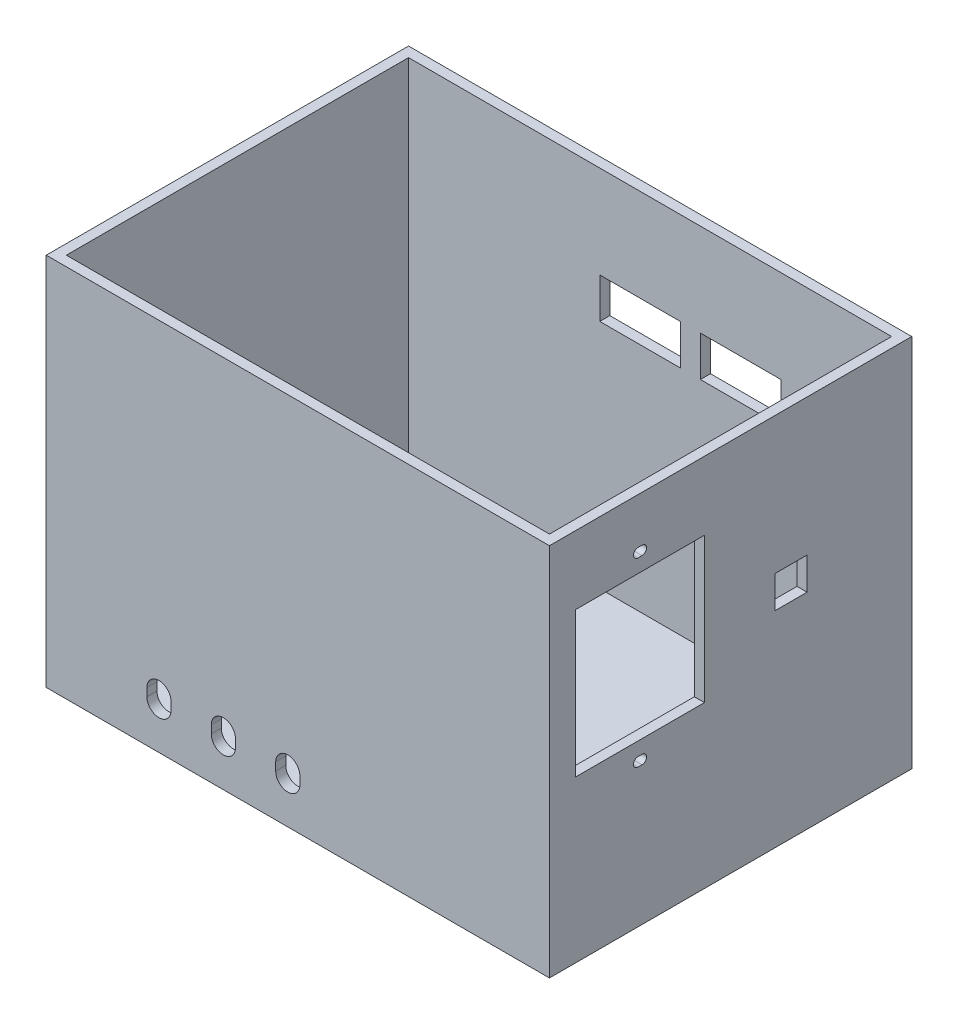
SolidWorks part; units mm, degrees
ref_plane "Front Plane" through (0, 0, 0) normal (0, 0, 1) x (1, 0, 0)
ref_plane "Top Plane" through (0, 0, 0) normal (0, 1, 0) x (1, 0, 0)
ref_plane "Right Plane" through (0, 0, 0) normal (1, 0, 0) x (0, 0, -1)
sketch "Sketch1" plane through (0, 0, 0) normal (0, 1, 0) x (1, 0, 0)
  line L0 (60, 42.5) -> (-60, 42.5)
  line L1 (62.5, 45) -> (-62.5, 45)
  line L2 (62.5, 45) -> (62.5, -45)
  line L3 (62.5, -45) -> (-62.5, -45)
  line L4 (-62.5, 45) -> (-62.5, -45)
  line L5 (62.5, 45) -> (-62.5, -45) construction
  line L6 (62.5, -45) -> (-62.5, 45) construction
  line L7 (-60, 42.5) -> (-60, -42.5)
  line L8 (60, -42.5) -> (-60, -42.5)
  line L9 (60, 42.5) -> (60, -42.5)
  point P0 (0, 0)
  dimension "D1" = 90
  dimension "D2" = 125
  dimension "D3" = 2.5
extrude "Boss-Extrude1" add sketch "Sketch1" along normal blind 2.5 contours L9 L0 L7 L8 | L1 L4 L3 L2 L0 L9 L8 L7 region at (0, 0, 0) region at (60.9597, 0, 0)
extrude "Boss-Extrude2" add sketch "Sketch1<3>" along normal blind 93
sketch "Sketch1<3>" plane through (0, 0, 0) normal (0, 1, 0) x (1, 0, 0) same geometry as "Sketch1"
sketch "Sketch2" plane through (62.5, 0, 0) normal (1, 0, 0) x (0, 0, -1)
  line L0 (0, 93) -> (0, 0) construction
  line L1 (-45, 93) -> (45, 93) construction
  line L2 (-23, 80.5) -> (-22, 80.5) construction
  line L3 (-6.5, 40) -> (-38.5, 40)
  line L4 (-6.5, 40) -> (-6.5, 76)
  line L5 (-6.5, 76) -> (-38.5, 76)
  line L6 (-38.5, 40) -> (-38.5, 76)
  line L7 (-6.5, 40) -> (-38.5, 76) construction
  line L8 (-6.5, 76) -> (-38.5, 40) construction
  line L11 (-23, 81.625) -> (-22, 81.625)
  line L12 (-23, 79.375) -> (-22, 79.375)
  line L13 (-48.2126, 58) -> (-0.6327, 58) construction
  line L14 (-23, 35.5) -> (-22, 35.5) construction
  line L15 (-23, 34.375) -> (-22, 34.375)
  line L16 (-23, 36.625) -> (-22, 36.625)
  arc A2 (-23, 81.625) -> (-23, 79.375) centre (-23, 80.5) ccw
  arc A3 (-22, 79.375) -> (-22, 81.625) centre (-22, 80.5) ccw
  arc A4 (-23, 34.375) -> (-23, 36.625) centre (-23, 35.5) cw
  arc A5 (-22, 36.625) -> (-22, 34.375) centre (-22, 35.5) cw
  point P5 (-22.5, 58)
  point P12 (-22.5, 80.5)
  point P17 (-22.5, 81.625)
  point P22 (-22.5, 35.5)
  point P35 (22.5, 35.5)
  point P42 (22.5, 80.5)
  point P47 (22.5, 58)
  dimension "D1" = 32
  dimension "D2" = 36
  dimension "D3" = 22.5
  dimension "D4" = 35
  dimension "D5" = 16
  dimension "D6" = 2.25
  dimension "D7" = 45
  dimension "D8" = 1
extrude "Cut-Extrude1" cut sketch "Sketch2" against normal blind 5
sketch "Sketch5" plane through (0, 0, 45) normal (0, 0, 1) x (1, 0, 0)
  line L0 (-62.5, 93) -> (-62.5, 0) construction
  line L1 (62.5, 0) -> (-62.5, 0) construction
  line L2 (-34.5, 10.5) -> (-34.5, 12.5) construction
  line L3 (-37.5, 10.5) -> (-37.5, 12.5)
  line L4 (-31.5, 10.5) -> (-31.5, 12.5)
  line L5 (-18.5, 10.5) -> (-18.5, 12.5) construction
  line L6 (-21.5, 10.5) -> (-21.5, 12.5)
  line L7 (-15.5, 10.5) -> (-15.5, 12.5)
  line L8 (-2.5, 10.5) -> (-2.5, 12.5) construction
  line L9 (-5.5, 10.5) -> (-5.5, 12.5)
  line L10 (0.5, 10.5) -> (0.5, 12.5)
  circle A0 centre (-34.5, 11.5) radius 3 construction
  arc A3 (-37.5, 10.5) -> (-31.5, 10.5) centre (-34.5, 10.5) ccw
  arc A4 (-31.5, 12.5) -> (-37.5, 12.5) centre (-34.5, 12.5) ccw
  arc A5 (-21.5, 10.5) -> (-15.5, 10.5) centre (-18.5, 10.5) ccw
  arc A6 (-15.5, 12.5) -> (-21.5, 12.5) centre (-18.5, 12.5) ccw
  arc A7 (-5.5, 10.5) -> (0.5, 10.5) centre (-2.5, 10.5) ccw
  arc A8 (0.5, 12.5) -> (-5.5, 12.5) centre (-2.5, 12.5) ccw
  point P8 (-34.5, 11.5)
  point P16 (-18.5, 11.5)
  point P23 (-2.5, 11.5)
  dimension "D1" = 6
  dimension "D2" = 28
  dimension "D3" = 11.5
  dimension "D4" = 6
  dimension "D5" = 2
  dimension "D6" = 3
extrude "Cut-Extrude2" cut sketch "Sketch5" against normal blind 10
sketch "Sketch6" plane through (62.5, 0, 0) normal (1, 0, 0) x (0, 0, -1)
  line L0 (45, 93) -> (45, 0) construction
  line L1 (11, 59) -> (19, 59)
  line L2 (11, 59) -> (11, 51)
  line L3 (11, 51) -> (19, 51)
  line L4 (19, 59) -> (19, 51)
  line L5 (11, 59) -> (19, 51) construction
  line L6 (11, 51) -> (19, 59) construction
  line L7 (-45, 93) -> (45, 93) construction
  line L8 (30, 35) -> (0, 35) construction
  line L9 (30, 35) -> (30, 75) construction
  line L10 (30, 75) -> (0, 75) construction
  line L11 (0, 35) -> (0, 75) construction
  line L12 (30, 35) -> (0, 75) construction
  line L13 (30, 75) -> (0, 35) construction
  point P0 (15, 55)
  point P7 (15, 55)
  dimension "D1" = 30
  dimension "D2" = 8
  dimension "D3" = 8
  dimension "D4" = 30
  dimension "D5" = 40
  dimension "D6" = 38
extrude "Cut-Extrude3" cut sketch "Sketch6" against normal blind 10
sketch "Sketch7" plane through (0, 0, -45) normal (0, 0, -1) x (-1, 0, 0)
  line L0 (-62.5, 0) -> (62.5, 0) construction
  line L1 (-32.5, 70) -> (-12.5, 70)
  line L2 (-32.5, 70) -> (-32.5, 60)
  line L3 (-32.5, 60) -> (-12.5, 60)
  line L4 (-12.5, 70) -> (-12.5, 60)
  line L5 (-32.5, 70) -> (-12.5, 60) construction
  line L6 (-32.5, 60) -> (-12.5, 70) construction
  line L7 (-62.5, 93) -> (-62.5, 0) construction
  line L8 (-7.5, 70) -> (12.5, 70)
  line L9 (-7.5, 70) -> (-7.5, 60)
  line L10 (-7.5, 60) -> (12.5, 60)
  line L11 (12.5, 70) -> (12.5, 60)
  line L12 (-7.5, 70) -> (12.5, 60) construction
  line L13 (-7.5, 60) -> (12.5, 70) construction
  point P0 (-22.5, 65)
  point P7 (2.5, 65)
  dimension "D1" = 10
  dimension "D2" = 20
  dimension "D3" = 65
  dimension "D4" = 40
  dimension "D5" = 2
extrude "Cut-Extrude4" cut sketch "Sketch7" against normal blind 10
